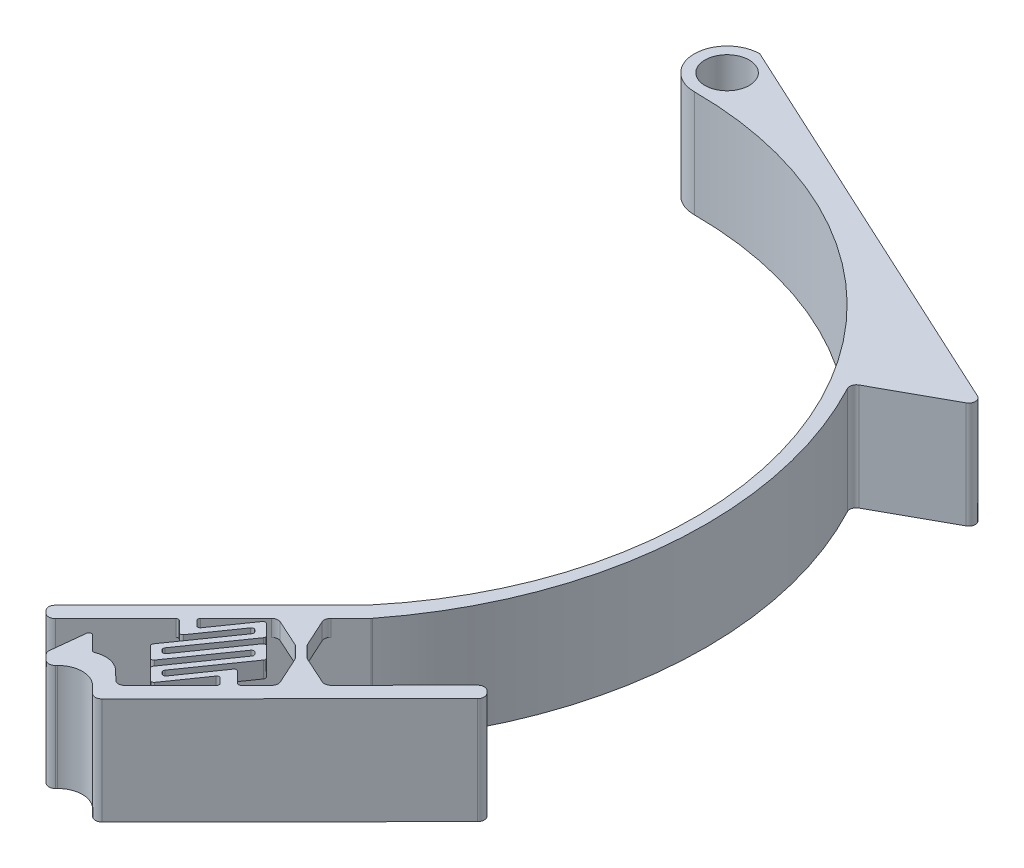
SolidWorks part; units mm, degrees
ref_plane "Front Plane" through (0, 0, 0) normal (0, 0, 1) x (1, 0, 0)
ref_plane "Top Plane" through (0, 0, 0) normal (0, 1, 0) x (1, 0, 0)
ref_plane "Right Plane" through (0, 0, 0) normal (1, 0, 0) x (0, 0, -1)
sketch "Sketch1" plane through (0, 0, 0) normal (0, 1, 0) x (1, 0, 0)
  line L0 (0, 0) -> (34.472, -28.9254) construction
  line L1 (0, 0) -> (0, -45) construction
  line L2 (0, 0) -> (63.5762, -53.3468) construction
  line L3 (0, 53) -> (50.8207, 29.4786)
  line L4 (50.8207, 29.4786) -> (40.3111, 23.6864)
  line L5 (0, 53) -> (0, 49)
  line L7 (0, 49) -> (0, 53)
  line L8 (34.472, -28.9254) -> (20.3504, -43.088)
  line L9 (20.3504, -43.088) -> (21.7666, -44.5002)
  line L10 (21.7666, -44.5002) -> (35.8883, -30.3376)
  line L11 (35.8883, -30.3376) -> (34.472, -28.9254)
  line L12 (30.2642, -52.9732) -> (28.8479, -51.561)
  line L13 (28.8479, -51.561) -> (50.0304, -30.3171)
  line L14 (50.0304, -30.3171) -> (51.4466, -31.7293)
  line L15 (51.4466, -31.7293) -> (30.2642, -52.9732)
  line L17 (24.0046, -45.3195) -> (29.2708, -50.5705)
  line L18 (35.083, -42.2442) -> (29.8168, -36.9932)
  line L19 (29.8168, -36.9932) -> (24.5858, -44.4869)
  line L21 (29.2708, -50.5705) -> (34.5017, -43.0768)
  line L22 (24.0046, -45.3195) -> (24.5858, -44.4869)
  line L24 (24.5858, -44.4869) -> (30.2601, -50.1448) construction
  line L25 (34.5017, -43.0768) -> (28.8274, -37.4189) construction
  line L26 (29.3086, -49.196) -> (33.9584, -42.535)
  line L27 (33.9584, -42.535) -> (33.321, -41.8995)
  line L28 (33.321, -41.8995) -> (28.6713, -48.5606)
  line L29 (28.6713, -48.5606) -> (29.3086, -49.196)
  line L30 (28.1279, -48.0187) -> (27.4906, -47.3833)
  line L31 (27.4906, -47.3833) -> (32.1403, -40.7222)
  line L32 (32.1403, -40.7222) -> (32.7777, -41.3577)
  line L33 (32.7777, -41.3577) -> (28.1279, -48.0187)
  line L34 (26.9472, -46.8415) -> (26.3099, -46.206)
  line L35 (26.3099, -46.206) -> (30.9596, -39.5449)
  line L36 (30.9596, -39.5449) -> (31.597, -40.1804)
  line L37 (31.597, -40.1804) -> (26.9472, -46.8415)
  line L38 (25.7665, -45.6642) -> (25.1292, -45.0287)
  line L39 (25.1292, -45.0287) -> (29.7789, -38.3677)
  line L40 (29.7789, -38.3677) -> (30.4163, -39.0031)
  line L41 (30.4163, -39.0031) -> (25.7665, -45.6642)
  line L42 (34.5017, -43.0768) -> (35.083, -42.2442)
  line L43 (24.5858, -44.4869) -> (25.1292, -45.0287) construction
  line L44 (25.7665, -45.6642) -> (26.3099, -46.206) construction
  line L45 (26.9472, -46.8415) -> (27.4906, -47.3833) construction
  line L46 (28.1279, -48.0187) -> (28.6713, -48.5606) construction
  line L47 (29.3086, -49.196) -> (29.852, -49.7378) construction
  line L48 (30.2396, -36.0026) -> (34.1313, -37.7648)
  line L49 (34.1313, -37.7648) -> (35.5475, -39.1769)
  line L50 (35.5475, -39.1769) -> (37.3209, -43.0635)
  line L51 (37.3209, -43.0635) -> (40.1452, -40.2309)
  line L52 (40.1452, -40.2309) -> (36.2536, -38.4688)
  line L53 (36.2536, -38.4688) -> (34.8373, -37.0566)
  line L54 (34.8373, -37.0566) -> (33.0639, -33.1701)
  line L55 (33.0639, -33.1701) -> (30.2396, -36.0026)
  line L56 (36.0041, -30.211) -> (35.8883, -30.3376)
  line L57 (20.3504, -43.088) -> (21.7666, -44.5002)
  line L58 (20.3504, -43.088) -> (14.7017, -48.7531)
  line L59 (21.7666, -44.5002) -> (16.118, -50.1653)
  line L60 (14.7017, -48.7531) -> (16.118, -50.1653)
  line L61 (16.118, -50.1653) -> (20.3545, -45.9165) construction
  line L62 (16.118, -50.1653) -> (19.6586, -53.6957) construction
  line L63 (20.3545, -45.9165) -> (23.8951, -49.4469) construction
  line L64 (19.6586, -53.6957) -> (23.8951, -49.4469) construction
  line L69 (30.2642, -52.9732) -> (27.4399, -55.8057)
  line L70 (27.4399, -55.8057) -> (23.8992, -52.2753)
  line L71 (28.8479, -51.561) -> (30.2642, -52.9732)
  line L72 (23.8992, -52.2753) -> (21.0749, -55.1078)
  line L73 (21.0749, -55.1078) -> (19.6586, -53.6957)
  line L74 (19.6586, -53.6957) -> (23.8951, -49.4469)
  line L75 (23.8951, -49.4469) -> (27.4358, -52.9773)
  line L76 (27.4358, -52.9773) -> (28.8479, -51.561)
  line L77 (28.8479, -51.561) -> (30.2642, -52.9732)
  line L82 (19.6586, -53.6957) -> (22.483, -50.8631)
  line L83 (22.483, -50.8631) -> (20.2169, -48.6037)
  line L84 (20.2169, -48.6037) -> (19.6586, -53.6957)
  line L85 (33.6299, -44.3257) -> (34.8496, -45.5419)
  line L86 (34.8496, -45.5419) -> (33.7905, -46.6041)
  line L87 (33.7905, -46.6041) -> (32.7581, -45.5747)
  line L88 (32.7581, -45.5747) -> (33.6299, -44.3257)
  line L89 (24.2379, -42.0218) -> (25.4576, -43.2379)
  line L90 (25.4576, -43.2379) -> (26.3295, -41.989)
  line L91 (26.3295, -41.989) -> (25.297, -40.9596)
  line L92 (25.297, -40.9596) -> (24.2379, -42.0218)
  circle A0 centre (0, 0) radius 45 construction
  arc A1 (0, 45) -> (34.472, -28.9254) centre (0, 0) cw
  arc A2 (0, 45) -> (0, 53) centre (0, 49) cw
  arc A4 (36.0041, -30.211) -> (0, 49) centre (-2.6664, 0) ccw
  circle A5 centre (0, 49) radius 2.7
  arc A6 (40.3111, 23.6864) -> (0, 49) centre (-2.6664, 0) ccw
  point P27 (0, 0)
  point P72 (33.2743, -46.0894)
  point P77 (23.7154, -43.619)
  point P78 (23.4558, -44.7723)
  point P80 (24.401, -44.3257)
  point P81 (23.7909, -45.1065)
  point P82 (0, 0)
  point P83 (0, 0)
  dimension "D1" = 90
  dimension "D5" = 56
  dimension "D6" = 5.4
  dimension "D9" = 2
  dimension "D2" = 50
  dimension "D3" = 8
  dimension "D4" = 2
  dimension "D7" = 12
  dimension "D8" = 2
  dimension "D10" = 1
  dimension "D11" = 10
  dimension "D12" = 10
  dimension "D13" = 0.9
  dimension "D14" = 1
  dimension "D15" = 0.4
  dimension "D16" = 0.4
  dimension "D17" = 10
  dimension "D18" = 1
  dimension "D19" = 4
  dimension "D20" = 4
  dimension "D21" = 1
  dimension "D22" = 20
  dimension "D23" = 30
  dimension "D24" = 2
  dimension "D25" = 4
  dimension "D26" = 0.1716
  dimension "D27" = 4
  dimension "D28" = 8
  dimension "D29" = 5
  dimension "D30" = 2
  dimension "D31" = 2
  dimension "D32" = 2
  dimension "D33" = 3.2
  dimension "D34" = 4
  dimension "D35" = 1.5
  dimension "D36" = 6
  dimension "D37" = 1.5
  dimension "D38" = 6
extrude "Boss-Extrude1" add sketch "Sketch1" along normal blind 13 contours A5 L5 A2 A1 A4 | A5 A4 L4 L3 L5 | L10 L11 L8 L9 | L53 L54 L10 L48 L49 L50 L13 L52 | L15 L14 L13 L12 | L13 L18 L19 L10 L17 L21 L29 L28 L27 L26 L32 L33 L30 L31 L36 L37 L34 L35 L40 L41 L38 L39 | L76 L75 L74 L73 L72 L70 L69 L12 | L83 L84 L74 | L58 L60 L59 L9 | L88 L85 L86 L87 | L92 L89 L90 L91 region at (34.2593, 0, -34.2496) region at (-0.974, 0, -52.35) region at (28.1193, 0, 36.7128) region at (18.2342, 0, 46.6267) region at (35.1924, 0, 38.1168) region at (29.5438, 0, 43.7818) region at (40.1473, 0, 41.6452) region at (24.9606, 0, 52.7905) region at (20.7862, 0, 51.0542)
sketch "Sketch2" plane through (-10.6921, 0, 10.7232) normal (-0.7061, 0, 0.7081) x (0.7081, 0, 0.7061)
  line L1 (46.8344, 11) -> (56.8344, 11)
  line L2 (46.8344, 11) -> (46.8344, 2)
  line L3 (46.8344, 2) -> (56.8344, 2)
  line L4 (56.8344, 11) -> (56.8344, 2)
  line L6 (48.9977, 13) -> (56.4344, 13) construction
  line L7 (46.8344, 13) -> (46.8344, 0) construction
  dimension "D1" = 10
  dimension "D2" = 9
  dimension "D3" = 2
extrude "Cut-Extrude1" cut sketch "Sketch2" against normal blind 23
fillet "Fillet2" radius 0.8 24 edges at (40.3111, 6.5, -23.6864) (50.8207, 6.5, -29.4786) (37.3209, 12, 43.0635) (35.5475, 12, 39.1769) (34.1313, 12, 37.7648) (30.2396, 12, 36.0026) (33.0639, 12, 33.1701) (40.1452, 1, 40.2309) (40.1452, 12, 40.2309) (34.8373, 1, 37.0566) (36.2536, 1, 38.4688) (34.8373, 12, 37.0566) (36.2536, 12, 38.4688) (50.0304, 6.5, 30.3171) (51.4466, 6.5, 31.7293) (27.4399, 6.5, 55.8057) (27.4358, 6.5, 52.9773) (19.6586, 6.5, 53.6957) (21.0749, 6.5, 55.1078) (16.118, 6.5, 50.1653) (14.7017, 6.5, 48.7531) (30.2396, 1, 36.0026) (33.0639, 1, 33.1701) (37.3209, 1, 43.0635)
fillet "Fillet4" radius 3 1 edges at (23.8992, 6.5, 52.2753)
fillet "Fillet5" radius 3 1 edges at (23.8951, 6.5, 49.4469)
fillet "Fillet6" radius 0.3 2 edges at (20.2169, 6.5, 48.6037) (22.483, 6.5, 50.8631)
sketch "Sketch3" plane through (0, 13, 0) normal (0, 1, 0) x (1, 0, 0)
  line L0 (33.6299, -44.3257) -> (35.083, -42.2442)
  line L1 (35.083, -42.2442) -> (33.9023, -41.0669)
  line L2 (35.083, -42.2442) -> (29.8168, -36.9932) construction
  line L3 (33.9023, -41.0669) -> (32.4492, -43.1484)
  line L4 (33.321, -41.8995) -> (28.6713, -48.5606) construction
  line L5 (32.4492, -43.1484) -> (33.6299, -44.3257)
  line L6 (25.4576, -43.2379) -> (24.0046, -45.3195)
  line L7 (24.0046, -45.3195) -> (25.1853, -46.4968)
  line L8 (24.0046, -45.3195) -> (29.2708, -50.5705) construction
  line L9 (25.1853, -46.4968) -> (26.6383, -44.4152)
  line L10 (30.4163, -39.0031) -> (25.7665, -45.6642) construction
  line L11 (26.6383, -44.4152) -> (25.4576, -43.2379)
  line L12 (30.9596, -39.5449) -> (31.597, -40.1804)
  line L13 (31.597, -40.1804) -> (32.1782, -39.3478)
  line L14 (32.1782, -39.3478) -> (31.5409, -38.7123)
  line L15 (31.5409, -38.7123) -> (30.9596, -39.5449)
  line L16 (30.9596, -39.5449) -> (28.1279, -48.0187)
  line L17 (28.1279, -48.0187) -> (27.4906, -47.3833)
  line L18 (27.4906, -47.3833) -> (26.9094, -48.2159)
  line L19 (26.9094, -48.2159) -> (27.5467, -48.8514)
  line L20 (27.5467, -48.8514) -> (28.1279, -48.0187)
  line L21 (24.2379, -42.0218) -> (25.4576, -43.2379) construction
  line L22 (33.6299, -44.3257) -> (34.8496, -45.5419) construction
  line L23 (26.3099, -46.206) -> (30.9596, -39.5449) construction
  line L24 (32.7777, -41.3577) -> (28.1279, -48.0187) construction
extrude "Cut-Extrude2" cut sketch "Sketch3" against normal through all contours L9 L11 L6 L7 | L19 L20 L17 L18 | L3 L5 L0 L1 | L14 L15 L12 L13 region at (33.7661, 13, 42.6963) region at (25.3215, 13, 44.8674) region at (31.5689, 13, 39.4464) region at (27.5186, 13, 48.1173)
fillet "Fillet7" radius 0.3 48 edges at (29.8168, 1, 36.9932) (31.5409, 1, 38.7123) (33.9023, 1, 41.0669) (33.0865, 1, 43.7839) (34.8496, 1, 45.5419) (32.7581, 1, 45.5747) (33.7905, 1, 46.6041) (32.1782, 1, 39.3478) (32.1403, 1, 40.7222) (32.7777, 1, 41.3577) (29.7789, 1, 38.3677) (30.4163, 1, 39.0031) (26.9094, 1, 48.2159) (27.5467, 1, 48.8514) (29.2708, 1, 50.5705) (28.6713, 1, 48.5606) (29.3086, 1, 49.196) (26.3099, 1, 46.206) (26.9472, 1, 46.8415) (25.1853, 1, 46.4968) (25.297, 1, 40.9596) (26.3295, 1, 41.989) (26.9472, 12, 46.8415) (33.0865, 12, 43.7839) (26.3295, 12, 41.989) (30.4163, 12, 39.0031) (32.7777, 12, 41.3577) (29.8168, 12, 36.9932) (32.1782, 12, 39.3478) (33.7905, 12, 46.6041) (34.8496, 12, 45.5419) (29.3086, 12, 49.196) (28.6713, 12, 48.5606) (25.1853, 12, 46.4968) (26.3099, 12, 46.206) (25.297, 12, 40.9596) (26.001, 1, 43.7798) (24.2379, 1, 42.0218) (24.2379, 12, 42.0218) (26.001, 12, 43.7798) (29.7789, 12, 38.3677) (31.5409, 12, 38.7123) (32.1403, 12, 40.7222) (33.9023, 12, 41.0669) (32.7581, 12, 45.5747) (27.5467, 12, 48.8514) (29.2708, 12, 50.5705) (26.9094, 12, 48.2159)
